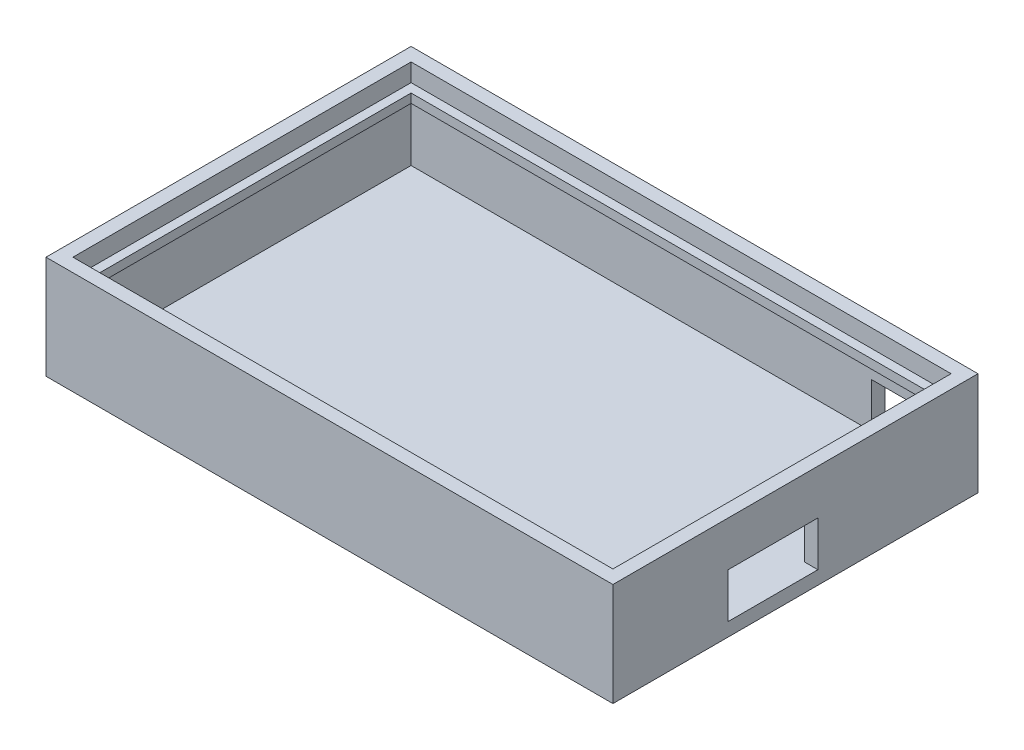
SolidWorks part; units mm, degrees
ref_plane "Front Plane" through (0, 0, 0) normal (0, 0, 1) x (1, 0, 0)
ref_plane "Top Plane" through (0, 0, 0) normal (0, 1, 0) x (1, 0, 0)
ref_plane "Right Plane" through (0, 0, 0) normal (1, 0, 0) x (0, 0, -1)
sketch "Sketch1" plane through (0, 0, 0) normal (0, 1, 0) x (1, 0, 0)
  line L0 (-63.2, 40.7) -> (63.2, 40.7)
  line L1 (-60, -37.5) -> (60, -37.5) construction
  line L2 (-60, -37.5) -> (-60, 37.5) construction
  line L3 (-60, 37.5) -> (60, 37.5) construction
  line L4 (60, -37.5) -> (60, 37.5) construction
  line L5 (-60, -37.5) -> (60, 37.5) construction
  line L6 (-60, 37.5) -> (60, -37.5) construction
  line L7 (11, -30) -> (56, -30) construction
  line L8 (11, -30) -> (11, 30) construction
  line L9 (11, 30) -> (56, 30) construction
  line L10 (56, -30) -> (56, 30) construction
  line L11 (11, -30) -> (56, 30) construction
  line L12 (11, 30) -> (56, -30) construction
  line L13 (63.2, -40.7) -> (63.2, 40.7)
  line L14 (-63.2, -40.7) -> (63.2, -40.7)
  line L15 (-63.2, -40.7) -> (-63.2, 40.7)
  line L17 (63.2, 5) -> (56, 5) construction
  line L18 (63.2, 5) -> (63.2, -15)
  line L19 (63.2, -15) -> (56, -15) construction
  line L20 (56, 5) -> (56, -15) construction
  point P0 (0, 0)
  point P6 (33.5, 0)
  point P23 (63.2, -5)
  dimension "D1" = 60
  dimension "D2" = 45
  dimension "D3" = 4
  dimension "D4" = 120
  dimension "D5" = 75
  dimension "D8" = 20
  dimension "D9" = 35
  dimension "D6" = 3.2
extrude "Boss-Extrude1" add sketch "Sketch1" along normal blind 3 contours L15 L14 L13 L0 region at (0, 0, 0)
sketch "Sketch2" plane through (0, 3, 0) normal (0, 1, 0) x (1, 0, 0)
  line L14 (63.2, -40.7) -> (63.2, 40.7) construction
  line L15 (-63.2, 40.7) -> (63.2, 40.7) construction
  line L16 (-63.2, -40.7) -> (-63.2, 40.7) construction
  line L17 (-63.2, -40.7) -> (63.2, -40.7) construction
  line L18 (63.2, -40.7) -> (63.2, 40.7)
  line L19 (-63.2, 40.7) -> (63.2, 40.7)
  line L20 (-63.2, -40.7) -> (-63.2, 40.7)
  line L21 (-63.2, -40.7) -> (63.2, -40.7)
  line L26 (60.2, -37.7) -> (60.2, 37.7)
  line L27 (-60.2, 37.7) -> (60.2, 37.7)
  line L28 (-60.2, -37.7) -> (-60.2, 37.7)
  line L29 (-60.2, -37.7) -> (60.2, -37.7)
  dimension "D1" = 3
extrude "Boss-Extrude2" add sketch "Sketch2" along normal blind 20
sketch "Sketch4" plane through (0, 3, 0) normal (0, 1, 0) x (1, 0, 0)
  line L0 (63.2, 5) -> (56, 5) construction
  line L1 (63.2, -15) -> (56, -15) construction
  line L2 (56, -30) -> (56, 30) construction
  line L3 (63.2, -40.7) -> (63.2, 40.7) construction
  line L4 (63.2, 5) -> (56, 5)
  line L5 (63.2, -15) -> (56, -15)
  line L6 (56, -15) -> (56, 5)
  line L7 (63.2, -15) -> (63.2, 5)
extrude "Cut-Extrude1" cut sketch "Sketch4" along normal blind 10
sketch "Sketch5" plane through (0, 3, 0) normal (0, 1, 0) x (1, 0, 0)
  line L0 (-60, 37.5) -> (60, 37.5) construction
  line L1 (42.5, 31.3326) -> (57.5, 31.3326)
  line L2 (42.5, 31.3326) -> (42.5, 43.6674)
  line L3 (42.5, 43.6674) -> (57.5, 43.6674)
  line L4 (57.5, 31.3326) -> (57.5, 43.6674)
  line L5 (42.5, 31.3326) -> (57.5, 43.6674) construction
  line L6 (42.5, 43.6674) -> (57.5, 31.3326) construction
  line L7 (60, -37.5) -> (60, 37.5) construction
  point P0 (50, 37.5)
  dimension "D1" = 10
  dimension "D2" = 15
extrude "Cut-Extrude2" cut sketch "Sketch5" along normal blind 10
sketch "Sketch6" plane through (0, 23, 0) normal (0, 1, 0) x (1, 0, 0)
  line L10 (60.2, -37.7) -> (60.2, 37.7) construction
  line L11 (60.2, 37.7) -> (-60.2, 37.7) construction
  line L12 (-60.2, 37.7) -> (-60.2, -37.7) construction
  line L13 (-60.2, -37.7) -> (60.2, -37.7) construction
  line L14 (-58.2, -35.7) -> (58.2, -35.7)
  line L15 (58.2, -35.7) -> (58.2, 35.7)
  line L16 (58.2, 35.7) -> (-58.2, 35.7)
  line L17 (-58.2, 35.7) -> (-58.2, -35.7)
  line L18 (-58.2, -35.7) -> (58.2, -35.7)
  line L19 (58.2, -35.7) -> (58.2, 35.7)
  line L20 (58.2, 35.7) -> (-58.2, 35.7)
  line L21 (-58.2, 35.7) -> (-58.2, -35.7)
  line L22 (60.2, -37.7) -> (60.2, 37.7)
  line L23 (60.2, 37.7) -> (-60.2, 37.7)
  line L24 (-60.2, 37.7) -> (-60.2, -37.7)
  line L25 (-60.2, -37.7) -> (60.2, -37.7)
  dimension "D1" = 2
extrude "Boss-Extrude3" add sketch "Sketch6" against normal blind 2 from offset 4 offset against normal yes
chamfer "Chamfer1" distance 2 angle 45 4 edges at (0, 17, 37.7) (60.2, 17, 0) (0, 17, -37.7) (-60.2, 17, 0)
